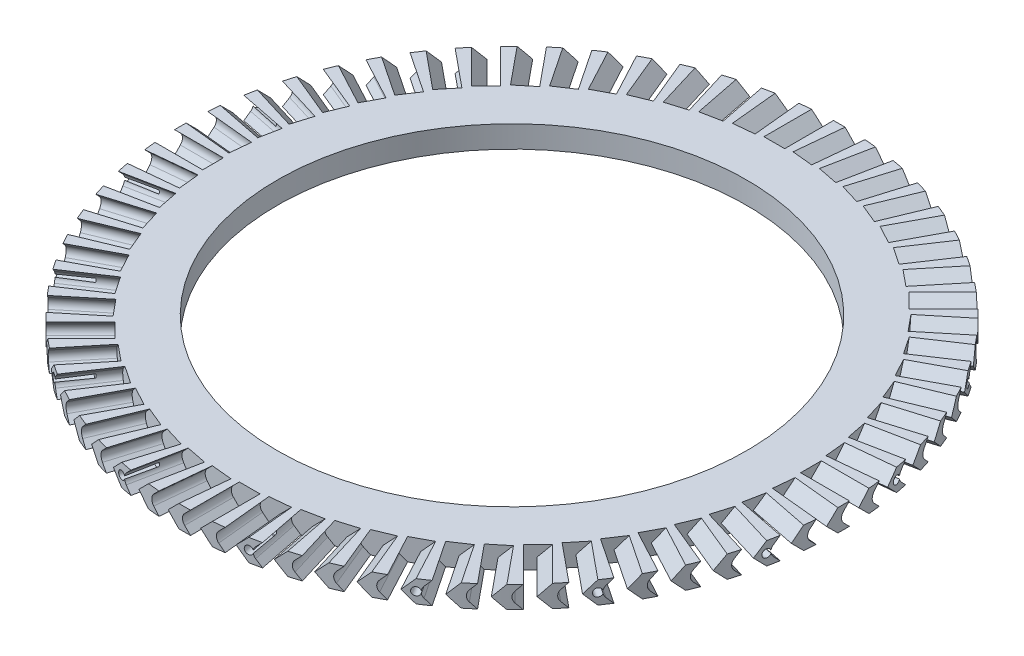
SolidWorks part; units mm, degrees
material "AISI 316 Annealed Stainless Steel Bar (SS)"
ref_plane "Front Plane" through (0, 0, 0) normal (0, 0, 1) x (1, 0, 0)
ref_plane "Top Plane" through (0, 0, 0) normal (0, 1, 0) x (1, 0, 0)
ref_plane "Right Plane" through (0, 0, 0) normal (1, 0, 0) x (0, 0, -1)
sketch "Sketch1" plane through (0, 0, 0) normal (0, 1, 0) x (1, 0, 0)
  circle A1 centre (0, 0) radius 142.6972
  circle A6 centre (0, 0) radius 101.6
  dimension "D1" = 203.2
  dimension "D2" = 285.3944
extrude "Disc" add sketch "Sketch1" along normal blind 4.7625 and the other way blind 4.7625
ref_plane "Plane1" through (-100.9022, 0, -100.9022) normal (-0.7071, 0, -0.7071) x (0, -1, 0)
sketch "Sketch2" plane through (-100.9022, 0, -100.9022) normal (-0.7071, 0, -0.7071) x (0, -1, 0)
  line L4 (4.7625, 0) -> (-4.7625, 0) construction
  line L7 (4.7625, -101.6) -> (4.7625, 101.6) construction
  line L10 (0, 0) -> (0, 3.175) construction
  line L11 (2.2451, 0.9299) -> (4.7625, 3.4474)
  line L12 (4.7625, -142.6972) -> (4.7625, 142.6972) construction
  line L13 (-2.2451, 0.9299) -> (-4.7625, 3.4474)
  line L14 (-4.7625, 142.6972) -> (-4.7625, -142.6972) construction
  line L15 (2.2451, 5.4201) -> (-4.7625, 12.4276)
  line L16 (-2.2451, 5.4201) -> (4.7625, 12.4276)
  line L17 (-4.7625, 12.4276) -> (-4.7625, 3.4474)
  line L18 (4.7625, 12.4276) -> (4.7625, 3.4474)
  circle A2 centre (0, 3.175) radius 3.175
  point P17 (-9.525, 12.0079)
  point P18 (-9.525, 3.5036)
  point P19 (0, 0)
  point P20 (0, 0)
  point P21 (-2.3813, 3.175)
  point P22 (0, 0)
  point P23 (0, 0)
  point P24 (-2.3813, 3.175)
  point P25 (0, 0)
  point P26 (0, 0)
  point P27 (0, 0)
  point P28 (2.8004, 0)
  point P33 (4.7625, 0)
  point P34 (0, 0)
  point P35 (0, 0)
  dimension "D1" = 6.35
  dimension "D2" = 45
  dimension "D3" = 45
extrude "Blades" cut sketch "Sketch2" against normal blind 21.1582 contours A2 | A2 L16 L15 L17 L13 | A2 L15 L16 | A2 L11 L18 L16 L15 region at (-106.0544, -3.1978, -95.7499) region at (-103.1472, 0, -98.6571) region at (-106.0544, 3.1978, -95.7499) region at (-105.613, 0, -96.1913)
pattern_circular "CirPattern1" count 64 over 360 about axis through (0, -4.7625, 0) along (0, 1, 0) of "Blades" reverse direction yes
hole_wizard "Tap Drill for #8-32 Tap1" positions "3DSketch2" profile "Sketch4" hole size "#8-32" standard "ANSI Inch"
sketch3d "3DSketch2"
  line L2 (-140.2524, 4.7625, 26.3014) -> (-140.2524, -4.7625, 26.3014) construction
  point P0 (-140.2524, 0, 26.3014)
sketch "Sketch4" plane through (-140.2524, 0, 26.3014) normal (0, 1, 0) x (0.1843, 0, 0.9829)
  line L0 (0, 0) -> (0, 13.7378)
  line L1 (0, 13.7378) -> (1.7272, 12.7)
  line L2 (1.7272, 12.7) -> (1.7272, 0)
  line L5 (1.7272, 0) -> (0, 0)
  line L10 (0, 13.7378) -> (-1.7272, 12.7) construction
  line L11 (0, -6.35) -> (0, 107.95) construction
  dimension "Hole Dia." = 3.4544
  dimension "Hole Depth" = 12.7
  dimension "Drill Angle" = 118
pattern_circular "CirPattern2" count 16 over 360 about axis through (0, -4.7625, 0) along (0, 1, 0) of "Tap Drill for #8-32 Tap1"
